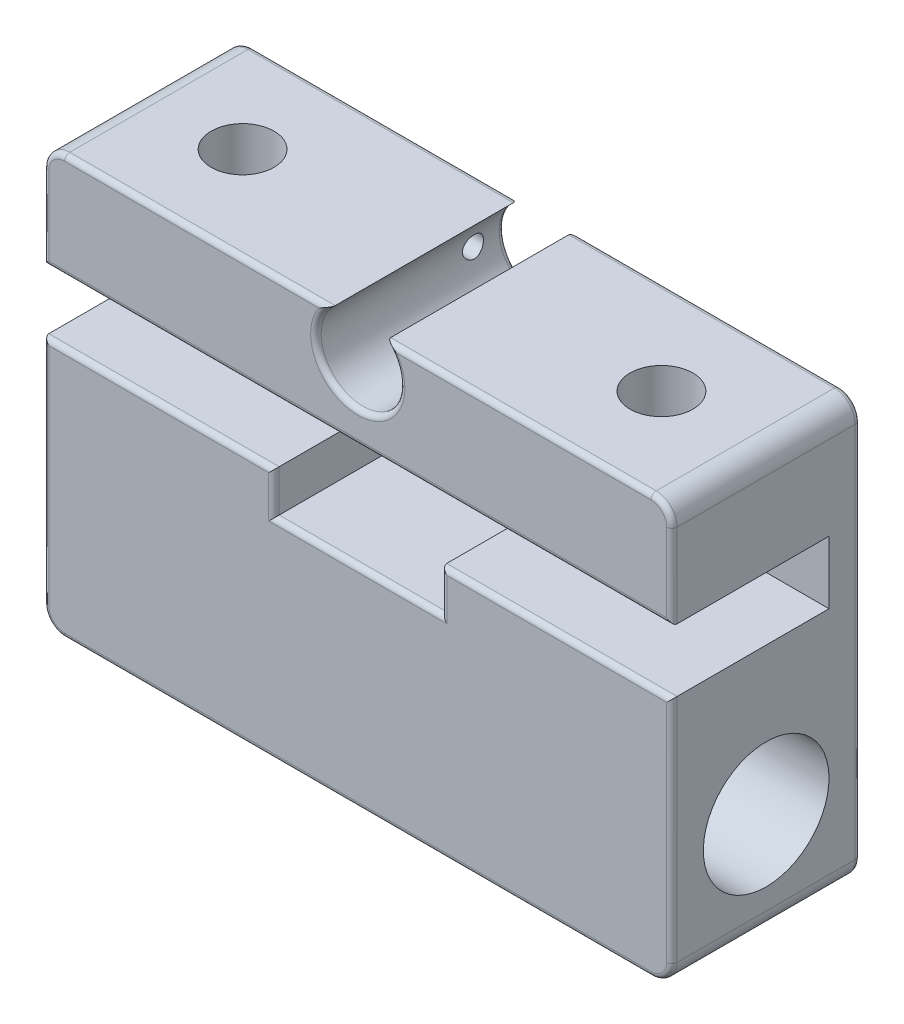
SolidWorks part; units mm, degrees
ref_plane "Front Plane" through (0, 0, 0) normal (0, 0, 1) x (1, 0, 0)
ref_plane "Top Plane" through (0, 0, 0) normal (0, 1, 0) x (1, 0, 0)
ref_plane "Right Plane" through (0, 0, 0) normal (1, 0, 0) x (0, 0, -1)
sketch "Sketch1" plane through (0, 0, 0) normal (0, 0, 1) x (1, 0, 0)
  line L1 (-30, 20) -> (30, 20)
  line L2 (-30, 20) -> (-30, -20)
  line L3 (-30, -20) -> (30, -20)
  line L4 (30, 20) -> (30, -20)
  line L5 (-30, 20) -> (30, -20) construction
  line L6 (-30, -20) -> (30, 20) construction
  point P0 (0, 0)
  dimension "D1" = 40
  dimension "D2" = 60
extrude "Boss-Extrude1" add sketch "Sketch1" along normal mid plane 18
sketch "Sketch2" plane through (-30, 0, 0) normal (-1, 0, 0) x (0, 0, 1)
  line L0 (0, 1.8022) -> (0, -4.9662) construction
  circle A0 centre (0, -10) radius 6
  dimension "D1" = 12
  dimension "D2" = 10
extrude "Cut-Extrude1" cut sketch "Sketch2" against normal through all
sketch "Sketch3" plane through (0, 0, 9) normal (0, 0, 1) x (1, 0, 0)
  line L0 (0, 0) -> (0, 7.3584) construction
  line L4 (30, -20) -> (30, 20)
  line L5 (30, 20) -> (-30, 20)
  line L6 (-30, 20) -> (-30, -20)
  line L7 (-30, -20) -> (30, -20)
  line L8 (30, -20) -> (30, 20) construction
  line L9 (30, 20) -> (-30, 20) construction
  line L10 (-30, 20) -> (-30, -20) construction
  line L11 (-30, -20) -> (30, -20) construction
  circle A0 centre (0, 17) radius 4
  dimension "D2" = 8
  dimension "D3" = 17
  dimension "D1" = 0
extrude "Cut-Extrude2" cut sketch "Sketch3" against normal through all
sketch "Sketch4" plane through (0, 0, 9) normal (0, 0, 1) x (1, 0, 0)
  line L0 (-30, 20) -> (-30, -20) construction
  line L1 (-30, 10) -> (30, 10)
  line L2 (-30, 10) -> (-30, 4)
  line L3 (-30, 4) -> (-8, 4)
  line L4 (30, 10) -> (30, 4)
  line L5 (30, -20) -> (30, 20) construction
  line L6 (8, 4) -> (30, 4)
  line L8 (-8, 4) -> (-8, 0)
  line L9 (-8, 0) -> (8, 0)
  line L10 (8, 4) -> (8, 0)
  dimension "D1" = 6
  dimension "D2" = 16
  dimension "D3" = 8
  dimension "D4" = 10
  dimension "D5" = 4
extrude "Cut-Extrude3" cut sketch "Sketch4" against normal blind 15
sketch "Sketch5" plane through (-30, 0, 0) normal (-1, 0, 0) x (0, 0, 1)
  line L0 (9, 20) -> (9, 10) construction
  line L1 (9, 20) -> (-9, 20) construction
  circle A0 centre (-6, 17) radius 1
  dimension "D1" = 2
  dimension "D2" = 15
  dimension "D3" = 3
extrude "Cut-Extrude4" cut sketch "Sketch5" against normal blind 29
sketch "Sketch6" plane through (-30, 0, 0) normal (-1, 0, 0) x (0, 0, 1)
  circle A0 centre (-6, 17) radius 1.5
  dimension "D1" = 3
extrude "Cut-Extrude5" cut sketch "Sketch6" against normal blind 5
sketch "Sketch7" plane through (0, 20, 0) normal (0, 1, 0) x (1, 0, 0)
  line L0 (-7.4904, 0) -> (6.3865, 0) construction
  line L1 (0, 5.874) -> (0, -4.849) construction
  circle A0 centre (-20, 0) radius 2
  circle A1 centre (20, 0) radius 2
  dimension "D1" = 4
  dimension "D2" = 20
extrude "Cut-Extrude6" cut sketch "Sketch7" against normal up to next
sketch "Sketch8" plane through (0, 20, 0) normal (0, 1, 0) x (1, 0, 0)
  line L0 (0, 5.0067) -> (0, -4.6125) construction
  circle A0 centre (-20, 0) radius 3
  circle A1 centre (20, 0) radius 3
  dimension "D1" = 6
extrude "Cut-Extrude7" cut sketch "Sketch8" against normal blind 5
fillet "Fillet1" radius 2 4 edges at (30, -20, 0) (30, 20, 0) (-30, -20, 0) (-30, 20, 0)
fillet "Fillet2" radius 0.5 28 edges at (29.4142, 19.4142, -9) (15.3229, 20, -9) (0, 13, -9) (-15.3229, 20, -9) (-29.4142, 19.4142, -9) (-30, 0, -9) (-29.4142, -19.4142, -9) (0, -20, -9) (29.4142, -19.4142, -9) (30, 0, -9) (-29.4142, -19.4142, 9) (-30, -7, 9) (-19, 4, 9) (-8, 2, 9) (0, 0, 9) (8, 2, 9) (19, 4, 9) (30, -7, 9) (29.4142, -19.4142, 9) (0, -20, 9) (0, 10, 9) (-30, 14, 9) (-29.4142, 19.4142, 9) (-15.3229, 20, 9) (0, 13, 9) (15.3229, 20, 9) (29.4142, 19.4142, 9) (30, 14, 9)
